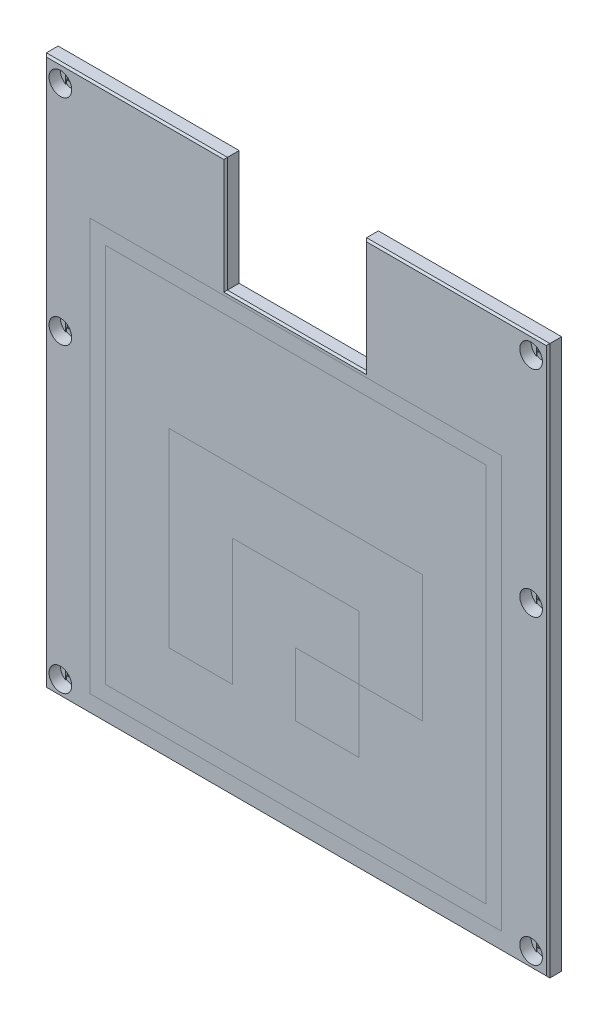
SolidWorks part; units mm, degrees
ref_plane "Front Plane" through (0, 0, 0) normal (0, 0, 1) x (1, 0, 0)
ref_plane "Top Plane" through (0, 0, 0) normal (0, 1, 0) x (1, 0, 0)
ref_plane "Right Plane" through (0, 0, 0) normal (1, 0, 0) x (0, 0, -1)
sketch "Sketch1" plane through (0, 0, 0) normal (0, 0, 1) x (1, 0, 0)
  line L0 (48, -68) -> (-48, -68) construction
  line L1 (56, -32.5) -> (56, -60) construction
  line L2 (56, 46) -> (56, -24.5) construction
  line L3 (-56, -24.5) -> (-56, 46) construction
  line L5 (-15, 54.4) -> (-15, 29) construction
  line L6 (-15, 29) -> (15, 29) construction
  line L7 (15, 29) -> (15, 54) construction
  line L8 (48, 54) -> (15, 54) construction
  line L9 (48, -68) -> (-48, -68) construction
  line L10 (56, -32.5) -> (56, -60) construction
  line L11 (56, 46) -> (56, -24.5) construction
  line L12 (-56, -24.5) -> (-56, 46) construction
  line L13 (-15, 54.4) -> (-48, 54.4) construction
  line L14 (-15, 54.4) -> (-15, 29) construction
  line L15 (-15, 29) -> (15, 29) construction
  line L16 (15, 29) -> (15, 54) construction
  line L17 (48, 54) -> (15, 54) construction
  line L18 (-15.5, 53.9) -> (-15.5, 28.5)
  line L19 (-55.5, 53.9) -> (-15.5, 53.9)
  line L20 (-55.5, 53.9) -> (-55.5, -67.5)
  line L21 (-55.5, -67.5) -> (55.75, -67.5)
  line L22 (55.75, 53.9) -> (55.75, -67.5)
  line L23 (-15.5, 28.5) -> (15.25, 28.5)
  line L24 (15.25, 28.5) -> (15.25, 53.9)
  line L25 (15.25, 53.9) -> (55.75, 53.9)
  circle A0 centre (-52, -64) radius 2.1 construction
  circle A1 centre (-52, 2.6) radius 2.1 construction
  circle A2 centre (52, 2.6) radius 2.1 construction
  circle A3 centre (52, 50) radius 2.1 construction
  circle A4 centre (-52, 50) radius 2.1 construction
  circle A5 centre (-52, -64) radius 2.1 construction
  circle A6 centre (-52, 2.6) radius 2.1 construction
  circle A7 centre (52, 2.6) radius 2.1 construction
  circle A8 centre (52, 50) radius 2.1 construction
  circle A9 centre (-52, 50) radius 2.1 construction
  circle A10 centre (-52, 50) radius 1.35
  circle A11 centre (-52, 2.6) radius 1.35
  circle A12 centre (-52, -64) radius 1.35
  circle A13 centre (52, 50) radius 1.35
  circle A14 centre (52, 2.6) radius 1.35
  circle A15 centre (52, -64) radius 1.35
  point P40 (-48, 54.4)
  dimension "D5" = 2.7
  dimension "D1" = 0.5
  dimension "D2" = 0.5
  dimension "D3" = 0.5
  dimension "D4" = 0.5
  dimension "D6" = 0.5
  dimension "D7" = 0.5
  dimension "D8" = 0.5
extrude "Boss-Extrude1" add sketch "Sketch1" along normal blind 3
sketch "Sketch2" plane through (0, 0, 3) normal (0, 0, 1) x (1, 0, 0)
  line L5 (15.25, 28.5) -> (-15.5, 28.5) construction
  line L8 (-45.5, -63.5) -> (45.5, -63.5)
  line L9 (-45.5, -63.5) -> (-45.5, 27.5)
  line L10 (-45.5, 27.5) -> (45.5, 27.5)
  line L11 (45.5, -63.5) -> (45.5, 27.5)
  line L31 (-42, 24) -> (-28, 24)
  line L32 (-42, 24) -> (-42, 10)
  line L33 (-42, 10) -> (-28, 10)
  line L34 (-28, 24) -> (-28, 10)
  line L35 (-28, 24) -> (-14, 24)
  line L36 (-28, 24) -> (-28, 10)
  line L37 (-28, 10) -> (-14, 10)
  line L38 (-14, 24) -> (-14, 10)
  line L39 (-14, 24) -> (0, 24)
  line L40 (-14, 24) -> (-14, 10)
  line L41 (-14, 10) -> (0, 10)
  line L42 (0, 24) -> (0, 10)
  line L43 (0, 24) -> (14, 24)
  line L44 (0, 24) -> (0, 10)
  line L45 (0, 10) -> (14, 10)
  line L46 (14, 24) -> (14, 10)
  line L47 (14, 24) -> (28, 24)
  line L48 (14, 24) -> (14, 10)
  line L49 (14, 10) -> (28, 10)
  line L50 (28, 24) -> (28, 10)
  line L51 (28, 24) -> (42, 24)
  line L52 (28, 24) -> (28, 10)
  line L53 (28, 10) -> (42, 10)
  line L54 (42, 24) -> (42, 10)
  line L55 (-42, 10) -> (-28, 10)
  line L56 (-42, 10) -> (-42, -4)
  line L57 (-42, -4) -> (-28, -4)
  line L58 (-28, 10) -> (-28, -4)
  line L59 (-28, -4) -> (-14, -4)
  line L60 (-28, -4) -> (-28, 10)
  line L61 (-28, 10) -> (-14, 10)
  line L62 (-14, -4) -> (-14, 10)
  line L63 (-14, -4) -> (0, -4)
  line L64 (-14, -4) -> (-14, 10)
  line L65 (-14, 10) -> (0, 10)
  line L66 (0, -4) -> (0, 10)
  line L67 (0, -4) -> (14, -4)
  line L68 (0, -4) -> (0, 10)
  line L69 (0, 10) -> (14, 10)
  line L70 (14, -4) -> (14, 10)
  line L71 (14, -4) -> (28, -4)
  line L72 (14, -4) -> (14, 10)
  line L73 (14, 10) -> (28, 10)
  line L74 (28, -4) -> (28, 10)
  line L75 (28, -4) -> (42, -4)
  line L76 (28, -4) -> (28, 10)
  line L77 (28, 10) -> (42, 10)
  line L78 (42, -4) -> (42, 10)
  line L79 (42, -4) -> (28, -4)
  line L80 (42, -4) -> (42, -18)
  line L81 (42, -18) -> (28, -18)
  line L82 (28, -4) -> (28, -18)
  line L83 (14, -4) -> (28, -4)
  line L84 (14, -4) -> (14, -18)
  line L85 (14, -18) -> (28, -18)
  line L86 (28, -4) -> (28, -18)
  line L87 (0, -4) -> (14, -4)
  line L88 (0, -4) -> (0, -18)
  line L89 (0, -18) -> (14, -18)
  line L90 (14, -4) -> (14, -18)
  line L91 (-14, -4) -> (0, -4)
  line L92 (-14, -4) -> (-14, -18)
  line L93 (-14, -18) -> (0, -18)
  line L94 (0, -4) -> (0, -18)
  line L95 (-28, -4) -> (-14, -4)
  line L96 (-28, -4) -> (-28, -18)
  line L97 (-28, -18) -> (-14, -18)
  line L98 (-14, -4) -> (-14, -18)
  line L99 (-42, -4) -> (-28, -4)
  line L100 (-42, -4) -> (-42, -18)
  line L101 (-42, -18) -> (-28, -18)
  line L102 (-28, -4) -> (-28, -18)
  line L103 (-42, -18) -> (-28, -18)
  line L104 (-42, -18) -> (-42, -32)
  line L105 (-42, -32) -> (-28, -32)
  line L106 (-28, -18) -> (-28, -32)
  line L107 (-28, -32) -> (-14, -32)
  line L108 (-28, -32) -> (-28, -18)
  line L109 (-28, -18) -> (-14, -18)
  line L110 (-14, -32) -> (-14, -18)
  line L111 (-14, -18) -> (0, -18)
  line L112 (-14, -18) -> (-14, -32)
  line L113 (-14, -32) -> (0, -32)
  line L114 (0, -18) -> (0, -32)
  line L115 (0, -32) -> (14, -32)
  line L116 (0, -32) -> (0, -18)
  line L117 (0, -18) -> (14, -18)
  line L118 (14, -32) -> (14, -18)
  line L119 (14, -32) -> (28, -32)
  line L120 (14, -32) -> (14, -18)
  line L121 (14, -18) -> (28, -18)
  line L122 (28, -32) -> (28, -18)
  line L123 (28, -32) -> (42, -32)
  line L124 (28, -32) -> (28, -18)
  line L125 (28, -18) -> (42, -18)
  line L126 (42, -32) -> (42, -18)
  line L127 (-42, -32) -> (-28, -32)
  line L128 (-42, -32) -> (-42, -46)
  line L129 (-42, -46) -> (-28, -46)
  line L130 (-28, -32) -> (-28, -46)
  line L131 (-28, -46) -> (-14, -46)
  line L132 (-28, -46) -> (-28, -32)
  line L133 (-28, -32) -> (-14, -32)
  line L134 (-14, -46) -> (-14, -32)
  line L135 (-14, -46) -> (0, -46)
  line L136 (-14, -46) -> (-14, -32)
  line L137 (-14, -32) -> (0, -32)
  line L138 (0, -46) -> (0, -32)
  line L139 (0, -46) -> (14, -46)
  line L140 (0, -46) -> (0, -32)
  line L141 (0, -32) -> (14, -32)
  line L142 (14, -46) -> (14, -32)
  line L143 (14, -46) -> (28, -46)
  line L144 (14, -46) -> (14, -32)
  line L145 (14, -32) -> (28, -32)
  line L146 (28, -46) -> (28, -32)
  line L147 (28, -46) -> (42, -46)
  line L148 (28, -46) -> (28, -32)
  line L149 (28, -32) -> (42, -32)
  line L150 (42, -46) -> (42, -32)
  line L151 (42, -46) -> (28, -46)
  line L152 (42, -46) -> (42, -60)
  line L153 (42, -60) -> (28, -60)
  line L154 (28, -46) -> (28, -60)
  line L155 (28, -60) -> (14, -60)
  line L156 (28, -60) -> (28, -46)
  line L157 (28, -46) -> (14, -46)
  line L158 (14, -60) -> (14, -46)
  line L159 (0, -46) -> (14, -46)
  line L160 (0, -46) -> (0, -60)
  line L161 (0, -60) -> (14, -60)
  line L162 (14, -46) -> (14, -60)
  line L163 (-14, -46) -> (0, -46)
  line L164 (-14, -46) -> (-14, -60)
  line L165 (-14, -60) -> (0, -60)
  line L166 (0, -46) -> (0, -60)
  line L167 (-28, -46) -> (-14, -46)
  line L168 (-28, -46) -> (-28, -60)
  line L169 (-28, -60) -> (-14, -60)
  line L170 (-14, -46) -> (-14, -60)
  line L171 (-42, -46) -> (-28, -46)
  line L172 (-42, -46) -> (-42, -60)
  line L173 (-42, -60) -> (-28, -60)
  line L174 (-28, -46) -> (-28, -60)
  point P3 (0, 27.5)
  point P52 (0, 0)
  point P58 (-45.5, -18)
  dimension "D1" = 1
  dimension "D2" = 91
  dimension "D3" = 14
sketch "Sketch3" plane through (0, 0, 3) normal (0, 0, 1) x (1, 0, 0)
  circle A0 centre (-52, 50) radius 2.5
  circle A1 centre (-52, 2.6) radius 2.5
  circle A2 centre (-52, -64) radius 2.5
  circle A3 centre (52, -64) radius 2.5
  circle A4 centre (52, 2.6) radius 2.5
  circle A5 centre (52, 50) radius 2.5
  dimension "D1" = 5
extrude "Cut-Extrude1" cut sketch "Sketch3" against normal blind 2.5
sketch "Sketch4" plane through (0, 0, 0) normal (0, 0, -1) x (-1, 0, 0)
  line L0 (-15.25, 28.5) -> (15.5, 28.5) construction
  line L1 (-45.5, -57.5) -> (45.5, -57.5)
  line L2 (-45.5, -57.5) -> (-45.5, 27.5)
  line L3 (-45.5, 27.5) -> (45.5, 27.5)
  line L4 (45.5, -57.5) -> (45.5, 27.5)
  line L5 (-45.5, -57.5) -> (45.5, 27.5) construction
  line L6 (-45.5, 27.5) -> (45.5, -57.5) construction
  line L7 (55.5, 53.9) -> (55.5, -67.5) construction
  line L8 (55.5, -67.5) -> (-55.75, -67.5) construction
  point P0 (0, -15)
  point P9 (0, 27.5)
  dimension "D1" = 1
  dimension "D2" = 10
  dimension "D3" = 10
extrude "Cut-Extrude2" cut sketch "Sketch4" against normal blind 1.5
sketch "Sketch5" plane through (0, 0, 0.5) normal (0, 0, 1) x (1, 0, 0)
  line L2 (-53.35, 47.8958) -> (-53.35, 52.1042)
  line L4 (-50.65, 47.8958) -> (-50.65, 52.1042)
  line L5 (-53.35, 47.8958) -> (-50.65, 52.1042) construction
  line L6 (-53.35, 52.1042) -> (-50.65, 47.8958) construction
  line L8 (-53.35, 0.4958) -> (-53.35, 4.7042)
  line L10 (-50.65, 0.4958) -> (-50.65, 4.7042)
  line L11 (-53.35, 0.4958) -> (-50.65, 4.7042) construction
  line L12 (-53.35, 4.7042) -> (-50.65, 0.4958) construction
  line L14 (-53.35, -66.1042) -> (-53.35, -61.8958)
  line L16 (-50.65, -66.1042) -> (-50.65, -61.8958)
  line L17 (-53.35, -66.1042) -> (-50.65, -61.8958) construction
  line L18 (-53.35, -61.8958) -> (-50.65, -66.1042) construction
  circle A0 centre (-52, 50) radius 2.5 construction
  circle A1 centre (-52, 50) radius 1.35 construction
  arc A2 (-50.65, 52.1042) -> (-53.35, 52.1042) centre (-52, 50) ccw
  arc A3 (-53.35, 47.8958) -> (-50.65, 47.8958) centre (-52, 50) ccw
  circle A4 centre (-52, 2.6) radius 2.5 construction
  circle A5 centre (-52, 2.6) radius 1.35 construction
  circle A6 centre (-52, 2.6) radius 2.5 construction
  arc A7 (-50.65, 4.7042) -> (-53.35, 4.7042) centre (-52, 2.6) ccw
  arc A8 (-53.35, 0.4958) -> (-50.65, 0.4958) centre (-52, 2.6) ccw
  circle A9 centre (-52, -64) radius 2.5 construction
  circle A10 centre (-52, -64) radius 1.35 construction
  circle A11 centre (-52, -64) radius 2.5 construction
  arc A12 (-50.65, -61.8958) -> (-53.35, -61.8958) centre (-52, -64) ccw
  arc A13 (-53.35, -66.1042) -> (-50.65, -66.1042) centre (-52, -64) ccw
  point P0 (-52, 50)
  point P10 (-52, 2.6)
  point P22 (-52, -64)
extrude "Cut-Extrude3" cut sketch "Sketch5" against normal blind 0.2
sketch "Sketch6" plane through (0, 0, 0.3) normal (0, 0, 1) x (1, 0, 0)
  line L0 (-50.65, -66.1042) -> (-50.65, -61.8958) construction
  line L1 (-53.35, -65.35) -> (-50.65, -65.35)
  line L2 (-53.35, -65.35) -> (-53.35, -62.65)
  line L3 (-53.35, -62.65) -> (-50.65, -62.65)
  line L4 (-50.65, -65.35) -> (-50.65, -62.65)
  line L5 (-53.35, -65.35) -> (-50.65, -62.65) construction
  line L6 (-53.35, -62.65) -> (-50.65, -65.35) construction
  line L7 (-50.65, 0.4958) -> (-50.65, 4.7042) construction
  line L8 (-53.35, 1.25) -> (-50.65, 1.25)
  line L9 (-53.35, 1.25) -> (-53.35, 3.95)
  line L10 (-53.35, 3.95) -> (-50.65, 3.95)
  line L11 (-50.65, 1.25) -> (-50.65, 3.95)
  line L12 (-53.35, 1.25) -> (-50.65, 3.95) construction
  line L13 (-53.35, 3.95) -> (-50.65, 1.25) construction
  line L14 (-50.65, 47.8958) -> (-50.65, 52.1042) construction
  line L15 (-53.35, 48.65) -> (-50.65, 48.65)
  line L16 (-53.35, 48.65) -> (-53.35, 51.35)
  line L17 (-53.35, 51.35) -> (-50.65, 51.35)
  line L18 (-50.65, 48.65) -> (-50.65, 51.35)
  line L19 (-53.35, 48.65) -> (-50.65, 51.35) construction
  line L20 (-53.35, 51.35) -> (-50.65, 48.65) construction
  arc A0 (-50.65, -64) -> (-53.35, -64) centre (-52, -64) ccw construction
  arc A1 (-50.65, 2.6) -> (-53.35, 2.6) centre (-52, 2.6) ccw construction
  arc A2 (-50.65, 50) -> (-53.35, 50) centre (-52, 50) ccw construction
  point P0 (-52, -64)
  point P11 (-52, 2.6)
  point P22 (-52, 50)
extrude "Cut-Extrude4" cut sketch "Sketch6" against normal blind 0.2
mirror "Mirror1" about plane through (0, 0, 0) normal (1, 0, 0) of "Cut-Extrude4", "Cut-Extrude3"
chamfer "Chamfer1" distance 0.4 angle 45 8 edges at (0.125, -67.5, 3) (55.75, -6.8, 3) (35.5, 53.9, 3) (15.25, 41.2, 3) (-0.125, 28.5, 3) (-15.5, 41.2, 3) (-35.5, 53.9, 3) (-55.5, -6.8, 3)
sketch "Sketch7" plane through (0, 0, 3) normal (0, 0, 1) x (1, 0, 0)
  line L0 (28, 24) -> (42, 24) construction
  line L1 (14, 24) -> (28, 24) construction
  line L2 (0, 24) -> (14, 24) construction
  line L3 (-14, 24) -> (0, 24) construction
  line L4 (-28, 24) -> (-14, 24) construction
  line L5 (-42, 24) -> (-28, 24) construction
  line L6 (-42, 24) -> (-42, 10) construction
  line L7 (-42, 10) -> (-42, -4) construction
  line L8 (-42, -4) -> (-42, -18) construction
  line L9 (-42, -18) -> (-42, -32) construction
  line L10 (-42, -32) -> (-42, -46) construction
  line L11 (-42, -46) -> (-42, -60) construction
  line L12 (-42, -60) -> (-28, -60) construction
  line L13 (-28, -60) -> (-14, -60) construction
  line L14 (-14, -60) -> (0, -60) construction
  line L15 (0, -60) -> (14, -60) construction
  line L16 (28, -60) -> (14, -60) construction
  line L17 (42, -60) -> (28, -60) construction
  line L18 (42, -46) -> (42, -60) construction
  line L19 (42, -46) -> (42, -32) construction
  line L20 (42, -32) -> (42, -18) construction
  line L21 (42, -4) -> (42, -18) construction
  line L22 (42, -4) -> (42, 10) construction
  line L23 (42, 24) -> (42, 10) construction
  line L24 (45.5, -63.5) -> (45.5, 27.5) construction
  line L25 (-45.5, -63.5) -> (45.5, -63.5) construction
  line L26 (-45.5, -63.5) -> (-45.5, 27.5) construction
  line L27 (-45.5, 27.5) -> (45.5, 27.5) construction
  line L28 (28, 24) -> (42, 24)
  line L29 (14, 24) -> (28, 24)
  line L30 (0, 24) -> (14, 24)
  line L31 (-14, 24) -> (0, 24)
  line L32 (-28, 24) -> (-14, 24)
  line L33 (-42, 24) -> (-28, 24)
  line L34 (-42, 24) -> (-42, 10)
  line L35 (-42, 10) -> (-42, -4)
  line L36 (-42, -4) -> (-42, -18)
  line L37 (-42, -18) -> (-42, -32)
  line L38 (-42, -32) -> (-42, -46)
  line L39 (-42, -46) -> (-42, -60)
  line L40 (-42, -60) -> (-28, -60)
  line L41 (-28, -60) -> (-14, -60)
  line L42 (-14, -60) -> (0, -60)
  line L43 (0, -60) -> (14, -60)
  line L44 (28, -60) -> (14, -60)
  line L45 (42, -60) -> (28, -60)
  line L46 (42, -46) -> (42, -60)
  line L47 (42, -46) -> (42, -32)
  line L48 (42, -32) -> (42, -18)
  line L49 (42, -4) -> (42, -18)
  line L50 (42, -4) -> (42, 10)
  line L51 (42, 24) -> (42, 10)
  line L52 (45.5, -63.5) -> (45.5, 27.5)
  line L53 (-45.5, -63.5) -> (45.5, -63.5)
  line L54 (-45.5, -63.5) -> (-45.5, 27.5)
  line L55 (-45.5, 27.5) -> (45.5, 27.5)
extrude "Cut-Extrude5" cut sketch "Sketch7" against normal blind 0.4
sketch "Sketch8" plane through (0, 0, 2.6) normal (0, 0, 1) x (1, 0, 0)
  line L0 (-42, -60) -> (42, -60) construction
  line L1 (42, -60) -> (42, 24) construction
  line L2 (42, 24) -> (-42, 24) construction
  line L3 (-42, 24) -> (-42, -60) construction
  line L4 (-45.5, -63.5) -> (45.5, -63.5)
  line L5 (45.5, -63.5) -> (45.5, 27.5)
  line L6 (45.5, 27.5) -> (-45.5, 27.5)
  line L7 (-45.5, 27.5) -> (-45.5, -63.5)
  line L8 (-45.5, -63.5) -> (45.5, -63.5)
  line L9 (45.5, -63.5) -> (45.5, 27.5)
  line L10 (45.5, 27.5) -> (-45.5, 27.5)
  line L11 (-45.5, 27.5) -> (-45.5, -63.5)
  line L12 (-42, -60) -> (42, -60)
  line L13 (42, -60) -> (42, 24)
  line L14 (42, 24) -> (-42, 24)
  line L15 (-42, 24) -> (-42, -60)
  dimension "D1" = 0
extrude "Boss-Extrude2" add sketch "Sketch8" along normal up to surface (0.4 mm away) separate body up to face at (0, -18, 3)
sketch "Sketch9" plane through (0, 0, 3) normal (0, 0, 1) x (1, 0, 0)
  line L0 (0, -46) -> (0, -32) construction
  line L1 (0, -46) -> (14, -46) construction
  line L2 (14, -46) -> (14, -32) construction
  line L3 (0, -32) -> (14, -32) construction
  line L4 (-14, -32) -> (-14, -18) construction
  line L5 (-14, -18) -> (0, -18) construction
  line L6 (0, -18) -> (14, -18) construction
  line L7 (14, -32) -> (14, -18) construction
  line L8 (14, -32) -> (28, -32) construction
  line L9 (28, -32) -> (28, -18) construction
  line L10 (28, -4) -> (28, -18) construction
  line L11 (14, -4) -> (28, -4) construction
  line L12 (0, -4) -> (14, -4) construction
  line L13 (-14, -4) -> (0, -4) construction
  line L14 (-28, -4) -> (-14, -4) construction
  line L15 (-28, -4) -> (-28, -18) construction
  line L16 (-28, -18) -> (-28, -32) construction
  line L17 (-28, -46) -> (-14, -46) construction
  line L18 (-14, -46) -> (-14, -32) construction
  line L19 (-28, -32) -> (-28, -46) construction
  line L20 (0, -46) -> (0, -32)
  line L21 (0, -46) -> (14, -46)
  line L22 (14, -46) -> (14, -32)
  line L23 (0, -32) -> (14, -32)
  line L24 (-14, -32) -> (-14, -18)
  line L25 (-14, -18) -> (0, -18)
  line L26 (0, -18) -> (14, -18)
  line L27 (14, -32) -> (14, -18)
  line L28 (14, -32) -> (28, -32)
  line L29 (28, -32) -> (28, -18)
  line L30 (28, -4) -> (28, -18)
  line L31 (14, -4) -> (28, -4)
  line L32 (0, -4) -> (14, -4)
  line L33 (-14, -4) -> (0, -4)
  line L34 (-28, -4) -> (-14, -4)
  line L35 (-28, -4) -> (-28, -18)
  line L36 (-28, -18) -> (-28, -32)
  line L37 (-28, -46) -> (-14, -46)
  line L38 (-14, -46) -> (-14, -32)
  line L39 (-28, -32) -> (-28, -46)
extrude "Cut-Extrude6" cut sketch "Sketch9" against normal blind 0.4 contours L23 L20 L21 L22 | L36 L39 L37 L38 L24 L25 L26 L27 L28 L29 L30 L31 L32 L33 L34 L35 region at (14.7, -25, 3) region at (7, -39, 3)
sketch "Sketch10" plane through (0, 0, 2.6) normal (0, 0, 1) x (1, 0, 0)
  line L0 (14, -32) -> (0, -32) construction
  line L1 (0, -32) -> (0, -46) construction
  line L2 (0, -46) -> (14, -46) construction
  line L3 (14, -46) -> (14, -32) construction
  line L4 (-28, -4) -> (-28, -46) construction
  line L5 (-28, -46) -> (-14, -46) construction
  line L6 (-14, -46) -> (-14, -18) construction
  line L7 (-14, -18) -> (14, -18) construction
  line L8 (14, -18) -> (14, -32) construction
  line L9 (14, -32) -> (28, -32) construction
  line L10 (28, -32) -> (28, -4) construction
  line L11 (28, -4) -> (-28, -4) construction
  line L12 (14, -32) -> (0, -32)
  line L13 (0, -32) -> (0, -46)
  line L14 (0, -46) -> (14, -46)
  line L15 (14, -46) -> (14, -32)
  line L16 (-28, -4) -> (-28, -46)
  line L17 (-28, -46) -> (-14, -46)
  line L18 (-14, -46) -> (-14, -18)
  line L19 (-14, -18) -> (14, -18)
  line L20 (14, -18) -> (14, -32)
  line L21 (14, -32) -> (28, -32)
  line L22 (28, -32) -> (28, -4)
  line L23 (28, -4) -> (-28, -4)
  line M1 (-28, -4) -> (-28, -46)
  line M2 (-28, -46) -> (-14, -46)
  line M3 (-14, -46) -> (-14, -18)
  line M4 (-14, -18) -> (14, -18)
  line M5 (14, -18) -> (14, -32)
  line M6 (14, -32) -> (28, -32)
  line M7 (28, -32) -> (28, -4)
  line M8 (28, -4) -> (-28, -4)
extrude "Boss-Extrude3" add sketch "Sketch10" along normal up to surface (0.4 mm away) separate body contours M8 M1 M2 M3 M4 M5 M6 M7 | L14 L15 L12 L13 region at (7, -39, 2.6) region at (14.7, -25, 2.6) up to face at (0, -18, 3)
